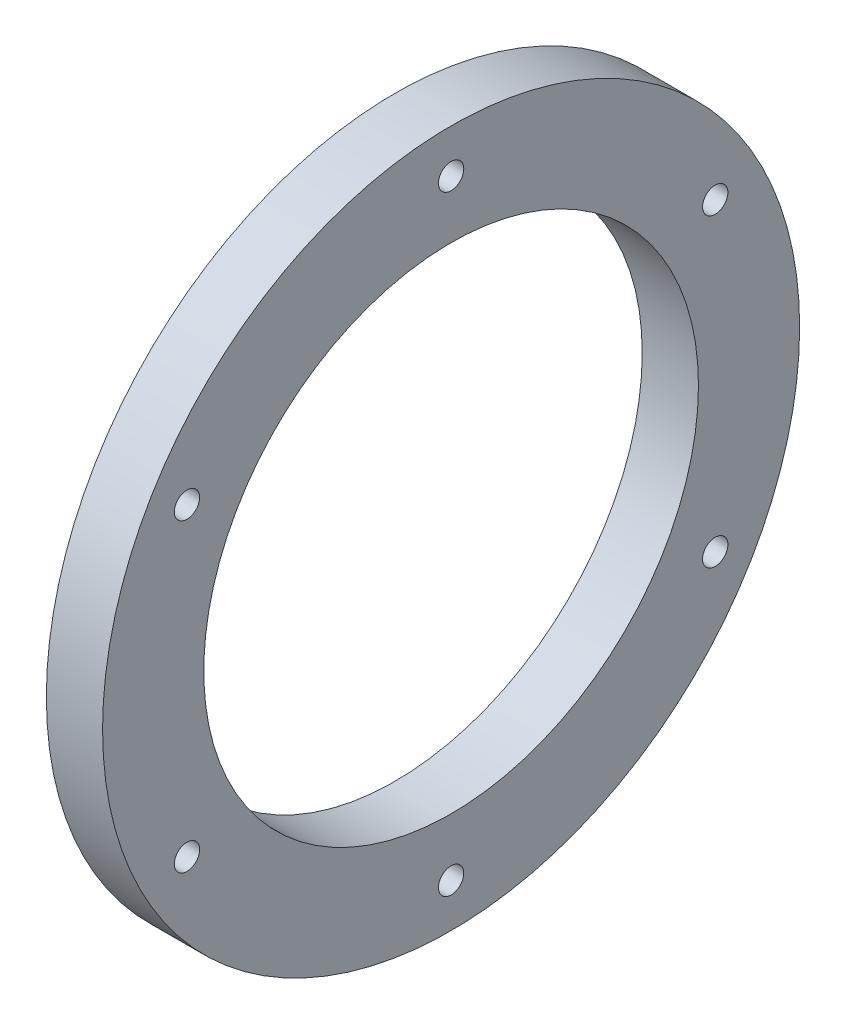
SolidWorks part; units mm, degrees
material "未指定"
ref_plane "正面" through (0, 0, 0) normal (0, 0, 1) x (1, 0, 0)
ref_plane "平面" through (0, 0, 0) normal (0, 1, 0) x (1, 0, 0)
ref_plane "右側面" through (0, 0, 0) normal (1, 0, 0) x (0, 0, -1)
sketch "ｽｹｯﾁ1" plane through (0, 0, 0) normal (1, 0, 0) x (0, 0, -1)
  circle A0 centre (0, 0) radius 62
  circle A1 centre (0, 0) radius 44
  dimension "D1" = 124
  dimension "D2" = 88
extrude "板 外形切り出し" add sketch "ｽｹｯﾁ1" along normal mid plane 10
hole_wizard "M4 通し穴" positions "ｽｹｯﾁ3" profile "ｽｹｯﾁ2" hole size "Ø4.5" standard "JIS" end condition through all
sketch "ｽｹｯﾁ3" plane through (5, 0, 0) normal (1, 0, 0) x (0, 0, -1)
  point P0 (0, 54.25)
  dimension "D1" = 54.25
sketch "ｽｹｯﾁ2" plane through (5, 54.25, 0) normal (0, 1, 0) x (0, 0, -1)
  line L0 (0, 0) -> (0, 11.3519)
  line L1 (0, 11.3519) -> (2.25, 10)
  line L2 (2.25, 10) -> (2.25, 0)
  line L5 (2.25, 0) -> (0, 0)
  line L10 (0, 11.3519) -> (-2.25, 10) construction
  line L11 (0, -6.35) -> (0, 107.95) construction
  dimension "穴の直径" = 4.5
  dimension "穴の深さ" = 10
  dimension "ﾄﾞﾘﾙ角度" = 118
ref_axis "中心軸" through (-5.5, 0, 0) along (1, 0, 0)
pattern_circular "M4 通し穴 等配" count 6 over 360 about axis through (-5.5, 0, 0) along (1, 0, 0) of "M4 通し穴"
equation "\"RING_OD\" = 124"
equation "\"D1@ｽｹｯﾁ1\" = \"RING_OD\""
equation "\"RING_ID\" = 88"
equation "\"D2@ｽｹｯﾁ1\" = \"RING_ID\""
equation "\"RING_T\" = 10"
equation "\"D1@板 外形切り出し\" = \"RING_T\""
equation "\"RING_PCD\" = 108.5"
equation "\"D1@ｽｹｯﾁ3\" = \"RING_PCD\" / 2"
